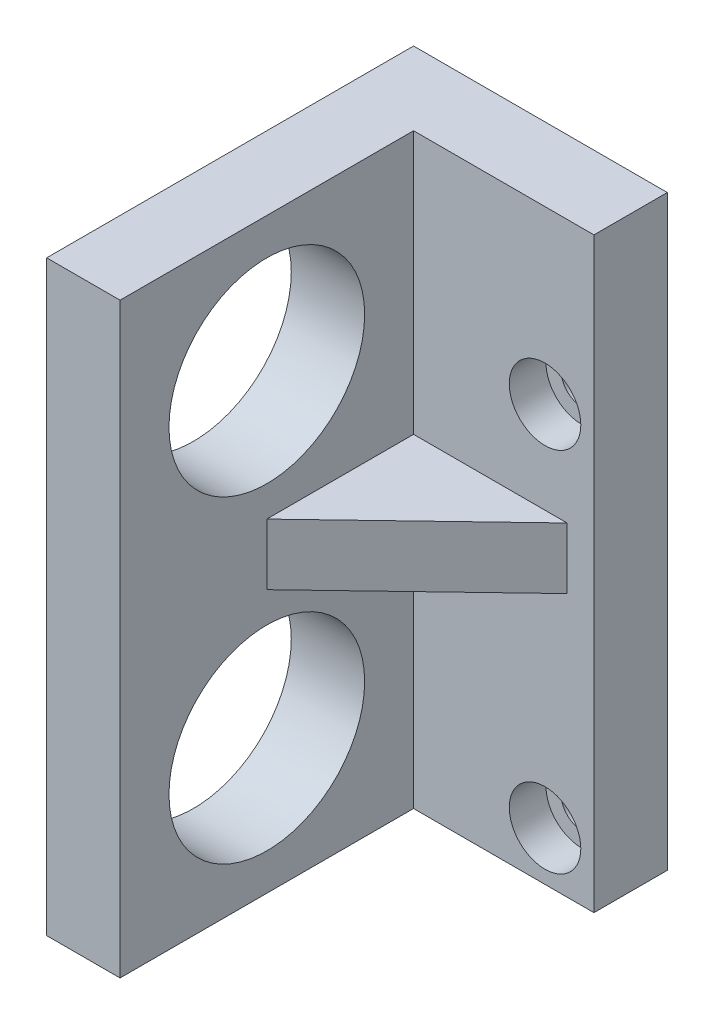
SolidWorks part; units mm, degrees
ref_plane "Front Plane" through (0, 0, 0) normal (0, 0, 1) x (1, 0, 0)
ref_plane "Top Plane" through (0, 0, 0) normal (0, 1, 0) x (1, 0, 0)
ref_plane "Right Plane" through (0, 0, 0) normal (1, 0, 0) x (0, 0, -1)
sketch "Sketch1" plane through (0, 0, 0) normal (0, 0, 1) x (1, 0, 0)
  line L0 (16.75, 48) -> (16.75, 0) construction
  line L1 (0, 0) -> (20.75, 0)
  line L2 (0, 0) -> (0, 48)
  line L3 (0, 48) -> (20.75, 48)
  line L4 (20.75, 0) -> (20.75, 48)
  circle A0 centre (16.75, 34) radius 1.675
  circle A1 centre (16.75, 4) radius 1.675
  dimension "D2" = 3.35
  dimension "D3" = 3.35
  dimension "D1" = 16.75
  dimension "D4" = 30
  dimension "D5" = 14
  dimension "D6" = 4
  dimension "D7" = 4
extrude "Boss-Extrude1" add sketch "Sketch1" along normal blind 6
sketch "Sketch2" plane through (0, 0, 0) normal (-1, 0, 0) x (0, 0, 1)
  line L1 (0, 48) -> (30, 48)
  line L2 (0, 48) -> (0, 0)
  line L3 (0, 0) -> (30, 0)
  line L4 (30, 48) -> (30, 0)
  point P4 (0, 0)
  dimension "D1" = 30
extrude "Boss-Extrude2" add sketch "Sketch2" against normal blind 6
sketch "Sketch3" plane through (0, 0, 0) normal (-1, 0, 0) x (0, 0, 1)
  line L0 (18, 48) -> (18, 0) construction
  line L1 (30, 48) -> (0, 48) construction
  line L2 (30, 0) -> (0, 0) construction
  line L3 (18, 24) -> (18.0919, 24) construction
  line L4 (0, 48) -> (0, 0) construction
  circle A0 centre (18, 37) radius 8
  circle A1 centre (18, 11) radius 8
  dimension "D1" = 16
  dimension "D2" = 13
  dimension "D3" = 18
extrude "Cut-Extrude1" cut sketch "Sketch3" against normal blind 6
sketch "Sketch4" plane through (0, 48, 0) normal (0, 1, 0) x (1, 0, 0)
  line L0 (6, -18) -> (6, -6)
  line L1 (6, -30) -> (6, -6) construction
  line L2 (6, -6) -> (18.5559, -6)
  line L3 (20.75, -6) -> (6, -6) construction
  line L4 (18.5559, -6) -> (6, -18)
extrude "Boss-Extrude3" add sketch "Sketch4" along normal blind 5 from offset 26.5 offset against normal yes
sketch "Sketch5" plane through (0, 0, 6) normal (0, 0, 1) x (1, 0, 0)
  circle A0 centre (16.75, 34) radius 2.925
  circle A1 centre (16.75, 4) radius 2.925
  dimension "D1" = 5.85
  dimension "D2" = 5.85
extrude "Cut-Extrude2" cut sketch "Sketch5" against normal blind 3
